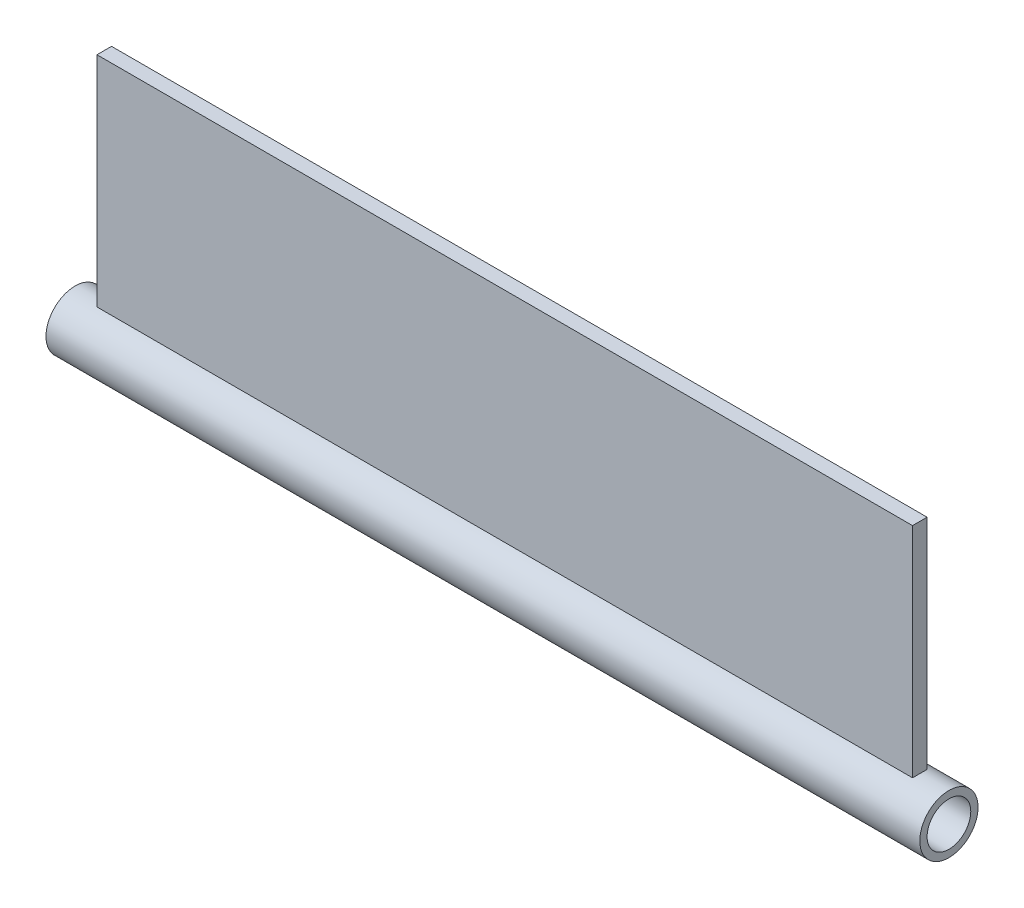
SolidWorks part; units mm, degrees
ref_plane "Front Plane" through (0, 0, 0) normal (0, 0, 1) x (1, 0, 0)
ref_plane "Top Plane" through (0, 0, 0) normal (0, 1, 0) x (1, 0, 0)
ref_plane "Right Plane" through (0, 0, 0) normal (1, 0, 0) x (0, 0, -1)
sketch "Sketch1" plane through (0, 0, 0) normal (1, 0, 0) x (0, 0, -1)
  circle A0 centre (0, 0) radius 5.08
  dimension "D1" = 10.16
extrude "Boss-Extrude1" add sketch "Sketch1" along normal blind 152.4
sketch "Sketch2" plane through (152.4, 0, 0) normal (1, 0, 0) x (0, 0, -1)
  circle A0 centre (0, 0) radius 3.81
  dimension "D1" = 7.62
extrude "Cut-Extrude1" cut sketch "Sketch2" against normal blind 152.4
sketch "Sketch3" plane through (0, 0, 0) normal (0, 0, 1) x (1, 0, 0)
  line L0 (152.4, 5.08) -> (0, 5.08) construction
  line L1 (147.32, 43.18) -> (5.08, 43.18)
  line L2 (147.32, 43.18) -> (147.32, 5.08)
  line L3 (147.32, 5.08) -> (5.08, 5.08)
  line L4 (5.08, 43.18) -> (5.08, 5.08)
  dimension "D1" = 142.24
  dimension "D2" = 38.1
  dimension "D3" = 5.08
extrude "Boss-Extrude2" add sketch "Sketch3" along normal blind 1.27 and the other way blind 1.27 separate body
